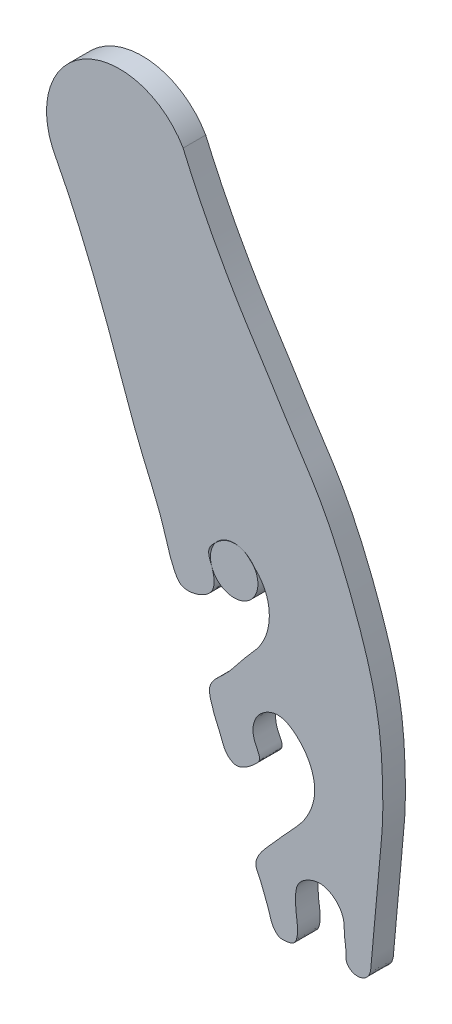
SolidWorks part; units mm, degrees
ref_plane "Front Plane" through (0, 0, 0) normal (0, 0, 1) x (1, 0, 0)
ref_plane "Top Plane" through (0, 0, 0) normal (0, 1, 0) x (1, 0, 0)
ref_plane "Right Plane" through (0, 0, 0) normal (1, 0, 0) x (0, 0, -1)
sketch "Sketch1" plane through (0, 0, 0) normal (0, 0, 1) x (1, 0, 0)
  line L0 (-59.0867, 75.1585) -> (-30.985, 91.1966) construction
  arc A0 (-30.985, 91.1966) -> (-59.0867, 75.1585) centre (-45.0359, 83.1776) ccw
  circle A1 centre (-19.6842, 15.8874) radius 5.2531
  spline S0 degree 3 poles (-59.0867, 75.1585) (-53.9346, 65.3789) (-47.4391, 48.6837) (-40.6887, 28.901) (-35.5304, 18.088) (-33.858, 10.7674) (-31.3998, 6.578) (-27.5219, 7.0158) (-23.9393, 9.2767) (-24.0764, 13.5358) (-26.0224, 16.8232) (-23.75, 19.2983) (-21.376, 21.2083) (-17.7857, 21.2749) (-15.8634, 19.3468) (-14.1859, 17.7777) (-12.3297, 15.0321) (-11.4508, 10.0831) (-13.3013, 4.5532) (-17.8022, 0.0202) (-20.9236, -4.7085) (-25.6849, -8.2473) (-24.7171, -12.3131) (-23.7108, -14.9774) (-22.4756, -17.5194) (-21.7662, -19.9617) (-19.5677, -21.6348) (-17.0547, -20.6234) (-15.5148, -19.3565) (-13.6022, -17.5442) (-14.9603, -15.2605) (-15.7736, -12.8169) (-15.0948, -9.8581) (-12.9329, -7.6437) (-9.3417, -6.4346) (-5.4914, -8.8976) (-2.613, -12.6524) (-1.5639, -16.9771) (-2.3681, -20.9531) (-4.2558, -24.701) (-7.9424, -28.4664) (-11.2364, -32.2564) (-13.9761, -35.2297) (-15.3063, -38.0057) (-13.9224, -40.2925) (-13.1614, -42.6176) (-11.9897, -45.2208) (-11.5081, -47.73) (-9.8646, -49.6721) (-8.0548, -49.436) (-6.1923, -49.1608) (-5.3962, -46.3293) (-5.9588, -43.5509) (-6.1685, -40.2748) (-5.9911, -36.9445) (-3.3185, -35.1012) (-0.2901, -34.2368) (2.9158, -35.7195) (4.8315, -38.7939) (4.5706, -42.0779) (5.2299, -44.5841) (4.9224, -46.927) (6.5933, -48.3134) (8.6329, -48.2844) (10.3966, -46.9215) (10.6173, -44.9495) (10.8674, -41.3466) (11.3633, -36.2233) (12.0194, -29.4872) (12.5336, -23.2803) (13.2669, -16.321) (13.2468, -8.5258) (12.77, 0.1153) (11.29, 8.7132) (8.5796, 17.7147) (4.6592, 28.1011) (-0.3774, 39.1219) (-6.8241, 48.353) (-11.9337, 56.8019) (-20.7413, 70.1683) (-26.9669, 81.8525) (-30.985, 91.1966) knots 0 0 0 0 0.087339 0.122518 0.154526 0.173634 0.178356 0.187752 0.197551 0.206694 0.216055 0.221692 0.228804 0.238708 0.243941 0.248249 0.255571 0.267719 0.283616 0.296048 0.313658 0.32674 0.33325 0.341962 0.348064 0.353714 0.360676 0.364715 0.372201 0.376189 0.381725 0.38858 0.395503 0.402402 0.410617 0.420879 0.432955 0.445135 0.451806 0.462304 0.475264 0.490195 0.498691 0.505626 0.510038 0.517164 0.523795 0.530641 0.536109 0.539904 0.543419 0.548956 0.558111 0.564731 0.573168 0.580566 0.586635 0.595642 0.604032 0.611503 0.619001 0.623087 0.627664 0.632725 0.637028 0.642687 0.646353 0.663712 0.680091 0.695898 0.709224 0.731217 0.752779 0.772428 0.794822 0.821373 0.853601 0.883019 0.903483 0.925781 1 1 1 1
  point P80 (-45.0359, 83.1776)
  point P85 (-19.8045, 15.5219)
  point P86 (-19.6842, 15.8874)
extrude "Boss-Extrude1" add sketch "Sketch1" along normal blind 5 contours A0 L0 | L0 S0 region at (-48.4393, 89.1409, 0) region at (-18.7202, 25.2883, 0)
ref_plane "Plane1" through (-12.2143, -6.9709, 0) normal (-0.8685, -0.4957, 0) x (0, 0, 1)
extrude "Boss-Extrude2" add sketch "Sketch1<3>" along normal blind 5 separate body contours S0 A1 region at (-19.6827, 15.8608, 0)
sketch "Sketch1<3>" plane through (0, 0, 0) normal (0, 0, 1) x (1, 0, 0) same geometry as "Sketch1"
